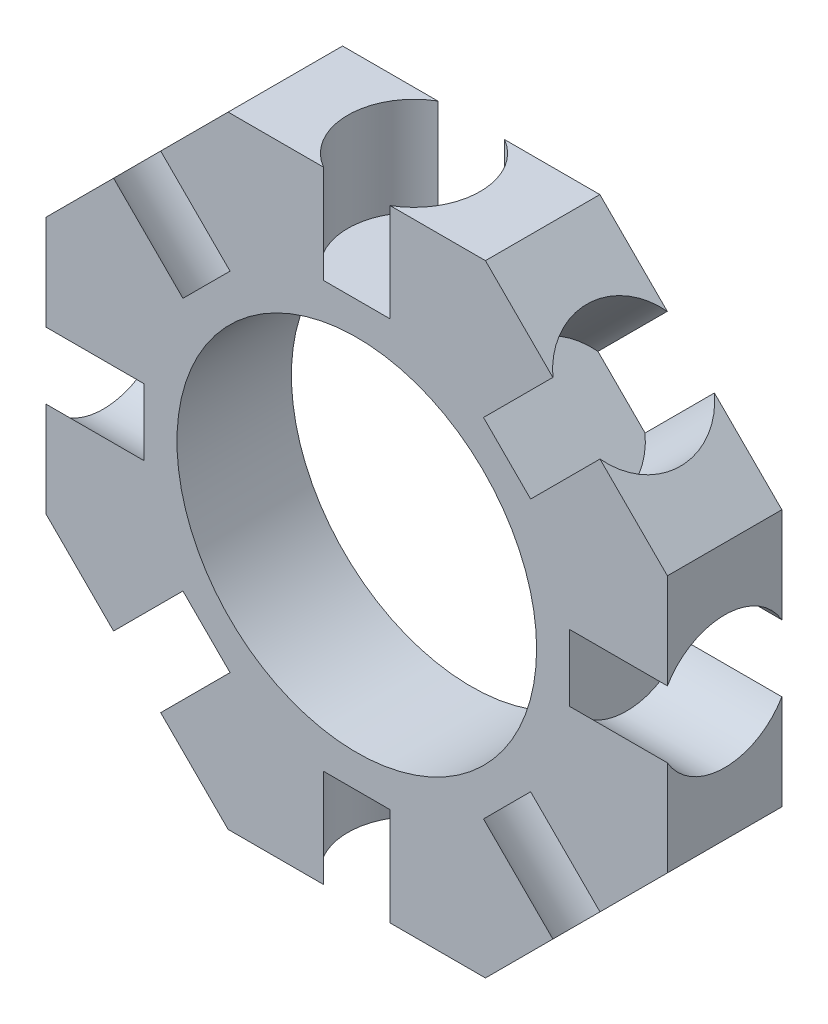
SolidWorks part; units mm, degrees
ref_plane "Top Plane" through (0, 0, 0) normal (0, 0, 1) x (1, 0, 0)
ref_plane "Right Plane" through (0, 0, 0) normal (0, 1, 0) x (1, 0, 0)
ref_plane "Front Plane" through (0, 0, 0) normal (1, 0, 0) x (0, 0, -1)
ref_axis "x-axis" through (-88.99, 0, 0) along (1, 0, 0)
ref_axis "y-axis" through (0, -55, 0) along (0, 1, 0)
ref_axis "z-axis" through (0, 0, 55) along (0, 0, -1)
sketch "Sketch1" plane through (0, 0, 0) normal (0, 0, 1) x (1, 0, 0)
  line L0 (7.8701, 19) -> (-7.8701, 19)
  line L1 (-19, 7.8701) -> (-19, -7.8701)
  line L2 (-19, -7.8701) -> (-7.8701, -19)
  line L3 (-7.8701, -19) -> (7.8701, -19)
  line L4 (7.8701, -19) -> (19, -7.8701)
  line L5 (19, -7.8701) -> (19, 7.8701)
  line L6 (19, 7.8701) -> (7.8701, 19)
  line L7 (-7.8701, 19) -> (-19, 7.8701)
  line L8 (-19, 0) -> (0, 0) construction
  circle A0 centre (0, 0) radius 11
  circle A1 centre (0, 0) radius 19 construction
  circle A2 centre (0, 0) radius 20.5655 construction
  dimension "D1" = 22
  dimension "D2" = 8
extrude "Boss-Extrude1" add sketch "Sketch1" along normal mid plane 7
sketch "Sketch2" plane through (0, -19, 0) normal (0, -1, 0) x (-1, 0, 0)
  circle A0 centre (0, 0) radius 4.05
  dimension "D1" = 8.1
extrude "Cut-Extrude3" cut sketch "Sketch2" against normal blind 6
pattern_circular "CirPattern1" count 8 over 360 about axis through (0, 0, 3.5) along (0, 0, 1) of "Cut-Extrude3"
